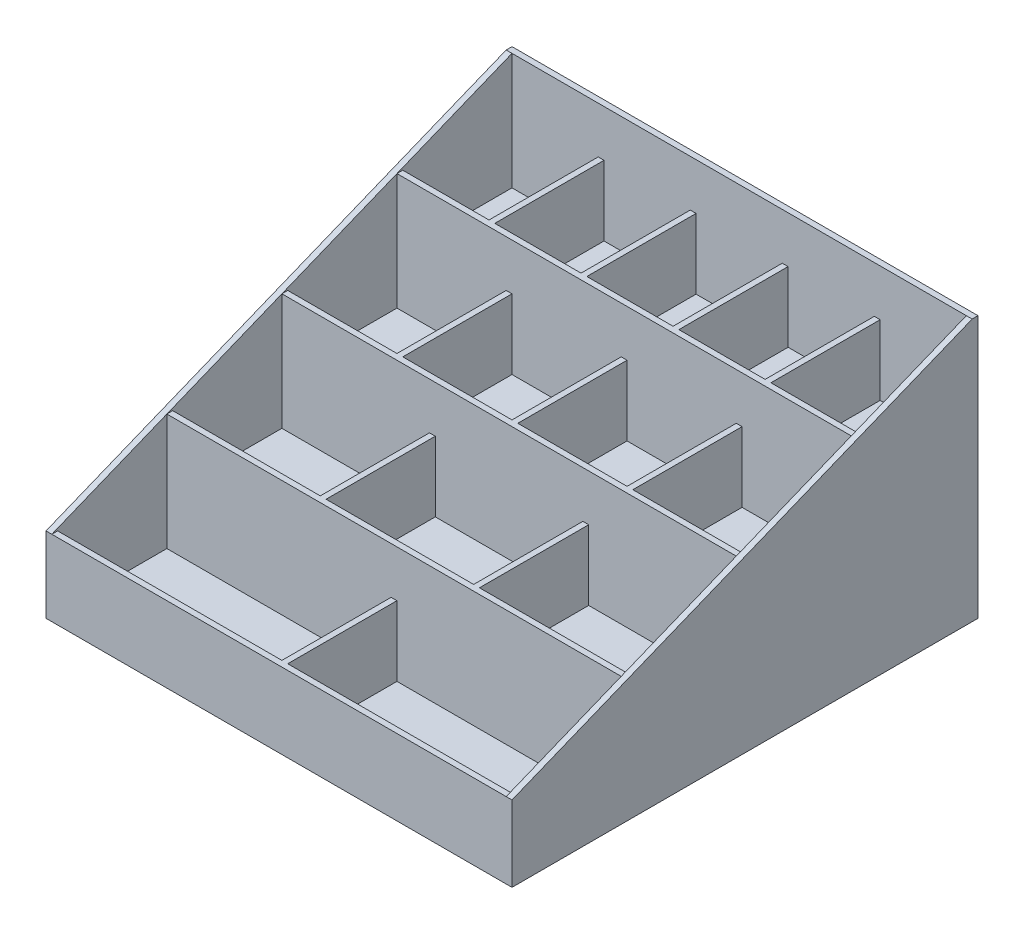
SolidWorks part; units mm, degrees
ref_plane "Front Plane" through (0, 0, 0) normal (0, 0, 1) x (1, 0, 0)
ref_plane "Top Plane" through (0, 0, 0) normal (0, 1, 0) x (1, 0, 0)
ref_plane "Right Plane" through (0, 0, 0) normal (1, 0, 0) x (0, 0, -1)
sketch "Sketch1" plane through (0, 0, 0) normal (1, 0, 0) x (0, 0, -1)
  line L1 (0, 0) -> (254, 0)
  line L3 (250.825, 117.475) -> (188.1188, 117.475)
  line L4 (188.1188, 117.475) -> (188.1188, 92.075)
  line L5 (188.1188, 92.075) -> (125.4125, 92.075)
  line L6 (125.4125, 92.075) -> (125.4125, 66.675)
  line L7 (125.4125, 66.675) -> (62.7062, 66.675)
  line L8 (62.7062, 66.675) -> (62.7062, 41.275)
  line L9 (62.7062, 41.275) -> (0, 41.275)
  line L10 (0, 41.275) -> (0, 15.875)
  line L11 (0, 15.875) -> (0, 0)
  line L13 (254, 117.475) -> (254, 0)
  line L14 (250.825, 117.475) -> (250.825, 142.875)
  line L15 (250.825, 142.875) -> (254, 142.875)
  line L16 (254, 142.875) -> (254, 117.475)
  point P13 (250.825, 142.875)
  point P15 (254, 117.475)
  point P17 (251.009, 142.875)
  dimension "D1" = 254
  dimension "D2" = 25.4
  dimension "D3" = 41.275
  dimension "D4" = 3.175
extrude "Boss-Extrude1" add sketch "Sketch1" along normal mid plane 254
sketch "Sketch3" plane through (0, 41.275, 0) normal (0, 1, 0) x (1, 0, 0)
  line L0 (127, 62.7062) -> (-127, 62.7062) construction
  line L1 (-123.825, 62.7063) -> (-1.5875, 62.7063)
  line L2 (-123.825, 62.7063) -> (-123.825, 3.175)
  line L3 (-123.825, 3.175) -> (-1.5875, 3.175)
  line L4 (-1.5875, 62.7063) -> (-1.5875, 3.175)
  line L5 (-123.825, 3.175) -> (-127, 3.175) construction
  line L6 (1.5875, 62.7063) -> (123.825, 62.7063)
  line L7 (1.5875, 62.7063) -> (1.5875, 3.175)
  line L8 (1.5875, 3.175) -> (123.825, 3.175)
  line L9 (123.825, 62.7063) -> (123.825, 3.175)
  line L10 (-127, 62.7062) -> (-127, 0) construction
  line L11 (-1.5875, 3.175) -> (1.5875, 3.175) construction
  line L12 (123.825, 3.175) -> (127, 3.175) construction
  line L13 (127, 62.7062) -> (127, 0) construction
  line L14 (-123.825, 3.175) -> (-123.825, 0) construction
  line L15 (127, 0) -> (-127, 0) construction
  dimension "D1" = 3.175
extrude "Cut-Extrude1" cut sketch "Sketch3" against normal blind 38.1
sketch "Sketch4" plane through (0, 66.675, 0) normal (0, 1, 0) x (1, 0, 0)
  line L0 (127, 125.4125) -> (-127, 125.4125) construction
  line L1 (-123.825, 125.4125) -> (-43.3917, 125.4125)
  line L2 (-123.825, 125.4125) -> (-123.825, 65.8812)
  line L3 (-123.825, 65.8812) -> (-43.3917, 65.8812)
  line L4 (-43.3917, 125.4125) -> (-43.3917, 65.8812)
  line L5 (-40.2167, 125.4125) -> (40.2167, 125.4125)
  line L6 (-40.2167, 125.4125) -> (-40.2167, 65.8812)
  line L7 (-40.2167, 65.8812) -> (40.2167, 65.8812)
  line L8 (40.2167, 125.4125) -> (40.2167, 65.8812)
  line L9 (43.3917, 125.4125) -> (123.825, 125.4125)
  line L10 (43.3917, 125.4125) -> (43.3917, 65.8812)
  line L11 (43.3917, 65.8812) -> (123.825, 65.8812)
  line L12 (123.825, 125.4125) -> (123.825, 65.8812)
  line L13 (-123.825, 62.7063) -> (-123.825, 3.175) construction
  line L14 (123.825, 3.175) -> (123.825, 62.7063) construction
  line L15 (-43.3917, 65.8812) -> (-40.2167, 65.8812) construction
  line L16 (1.5875, 62.7063) -> (-1.5875, 62.7063) construction
  dimension "D1" = 3
extrude "Cut-Extrude2" cut sketch "Sketch4" against normal blind 38.1
sketch "Sketch5" plane through (0, 92.075, 0) normal (0, 1, 0) x (1, 0, 0)
  line L0 (61.1187, 128.5875) -> (64.2938, 128.5875) construction
  line L1 (-123.825, 188.1188) -> (-64.2938, 188.1188)
  line L2 (-123.825, 188.1188) -> (-123.825, 128.5875)
  line L3 (-123.825, 128.5875) -> (-64.2938, 128.5875)
  line L4 (-64.2938, 188.1188) -> (-64.2938, 128.5875)
  line L5 (127, 188.1187) -> (-127, 188.1187) construction
  line L6 (-123.825, 125.4125) -> (-123.825, 65.8812) construction
  line L8 (-61.1187, 188.1188) -> (-1.5875, 188.1188)
  line L9 (-61.1187, 188.1188) -> (-61.1187, 128.5875)
  line L10 (-61.1187, 128.5875) -> (-1.5875, 128.5875)
  line L11 (-1.5875, 188.1188) -> (-1.5875, 128.5875)
  line L12 (1.5875, 188.1188) -> (61.1187, 188.1188)
  line L13 (1.5875, 188.1188) -> (1.5875, 128.5875)
  line L14 (1.5875, 128.5875) -> (61.1187, 128.5875)
  line L15 (61.1187, 188.1188) -> (61.1187, 128.5875)
  line L16 (64.2938, 188.1188) -> (123.825, 188.1188)
  line L17 (64.2938, 188.1188) -> (64.2938, 128.5875)
  line L18 (64.2938, 128.5875) -> (123.825, 128.5875)
  line L19 (123.825, 188.1188) -> (123.825, 128.5875)
  line L25 (127, 125.4125) -> (123.825, 125.4125) construction
  line L27 (123.825, 128.5875) -> (123.825, 125.4125) construction
  line L28 (127, 125.4125) -> (-127, 125.4125) construction
  line L30 (123.825, 65.8812) -> (123.825, 125.4125) construction
  dimension "D1" = 4
extrude "Cut-Extrude3" cut sketch "Sketch5" against normal blind 38.1
sketch "Sketch6" plane through (0, 117.475, 0) normal (0, 1, 0) x (1, 0, 0)
  line L0 (127, 188.1188) -> (-127, 188.1188) construction
  line L1 (-123.825, 250.825) -> (-76.835, 250.825)
  line L2 (-123.825, 250.825) -> (-123.825, 191.2937)
  line L3 (-123.825, 191.2937) -> (-76.835, 191.2937)
  line L4 (-76.835, 250.825) -> (-76.835, 191.2937)
  line L6 (-123.825, 191.2937) -> (-123.825, 188.1187) construction
  line L8 (-123.825, 188.1188) -> (-127, 188.1188) construction
  line L9 (-123.825, 188.1188) -> (-123.825, 128.5875) construction
  line L10 (-26.67, 250.825) -> (-26.67, 191.2937)
  line L11 (-73.66, 250.825) -> (-26.67, 250.825)
  line L12 (-73.66, 250.825) -> (-73.66, 191.2937)
  line L13 (-73.66, 191.2937) -> (-26.67, 191.2937)
  line L14 (23.495, 250.825) -> (23.495, 191.2937)
  line L15 (-23.495, 250.825) -> (23.495, 250.825)
  line L16 (-23.495, 250.825) -> (-23.495, 191.2937)
  line L17 (-23.495, 191.2937) -> (23.495, 191.2937)
  line L18 (73.66, 250.825) -> (73.66, 191.2937)
  line L19 (26.67, 250.825) -> (73.66, 250.825)
  line L20 (26.67, 250.825) -> (26.67, 191.2937)
  line L21 (26.67, 191.2937) -> (73.66, 191.2937)
  line L22 (123.825, 250.825) -> (123.825, 191.2937)
  line L23 (76.835, 250.825) -> (123.825, 250.825)
  line L24 (76.835, 250.825) -> (76.835, 191.2937)
  line L25 (76.835, 191.2937) -> (123.825, 191.2937)
  line L26 (123.825, 250.825) -> (127, 250.825) construction
  line L28 (-76.835, 250.825) -> (-73.66, 250.825) construction
  line L29 (127, 250.825) -> (-127, 250.825) construction
  line L30 (127, 250.825) -> (127, 188.1188) construction
  point P5 (0, 0)
  point P10 (0, 0)
  point P34 (0, 0)
  point P35 (0, 0)
  dimension "D1" = 5
extrude "Cut-Extrude4" cut sketch "Sketch6" against normal blind 38.1
sketch "Sketch7" plane through (127, 0, 0) normal (1, 0, 0) x (0, 0, -1)
  line L0 (0, 41.275) -> (250.825, 142.875)
  line L2 (250.825, 142.875) -> (250.825, 41.275)
  line L3 (250.825, 41.275) -> (0, 41.275)
  point P3 (250.825, 142.875)
  point P5 (174.1096, 117.475)
  point P7 (260.6972, 117.475)
  point P8 (254, 161.4089)
  point P9 (0, 0)
  point P13 (0, 0)
extrude "Boss-Extrude2" add sketch "Sketch7" against normal blind 3.175
mirror "Mirror1" about plane through (0, 0, 0) normal (1, 0, 0) of "Boss-Extrude2"
